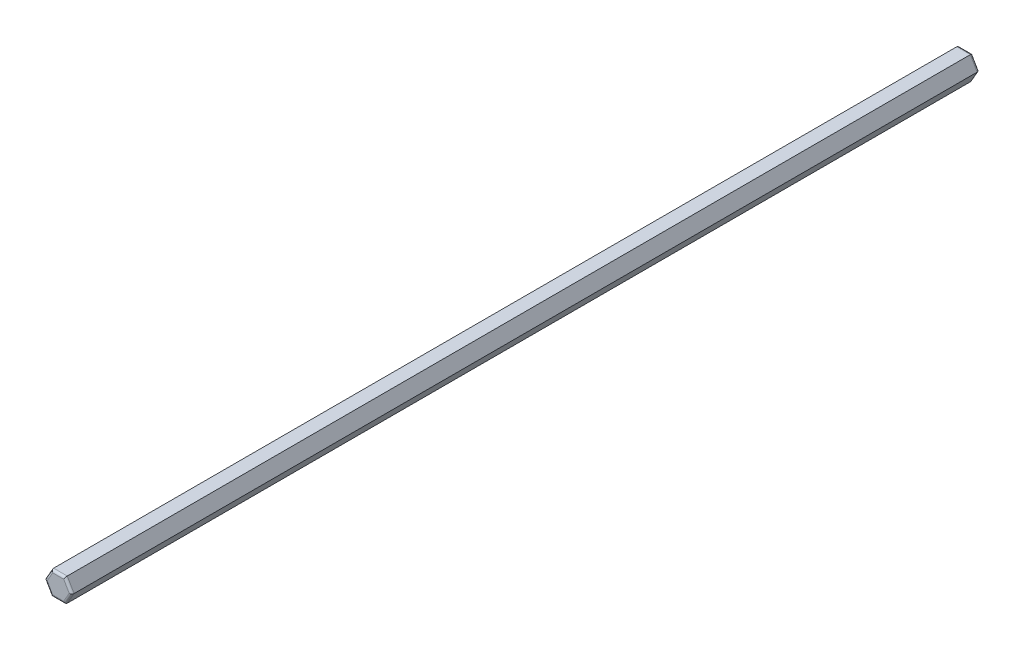
SolidWorks part; units mm, degrees
ref_plane "Front Plane" through (0, 0, 0) normal (0, 0, 1) x (1, 0, 0)
ref_plane "Top Plane" through (0, 0, 0) normal (0, 1, 0) x (1, 0, 0)
ref_plane "Right Plane" through (0, 0, 0) normal (1, 0, 0) x (0, 0, -1)
sketch "Sketch2" plane through (0, 0, 0) normal (0, 0, 1) x (1, 0, 0)
  line L1 (-0.75, 1.299) -> (-1.5, 0)
  line L2 (-1.5, 0) -> (-0.75, -1.299)
  line L3 (-0.75, -1.299) -> (0.75, -1.299)
  line L4 (0.75, -1.299) -> (1.5, 0)
  line L5 (1.5, 0) -> (0.75, 1.299)
  line L6 (0.75, 1.299) -> (-0.75, 1.299)
  circle A0 centre (0, 0) radius 1.299 construction
  dimension "D1" = 3
extrude "Boss-Extrude1" add sketch "Sketch2" along normal blind 50 and the other way blind 50
fillet "Fillet1" radius 0.25 12 edges at (1.125, -0.6495, -50) (0, -1.299, -50) (-1.125, -0.6495, -50) (-1.125, 0.6495, -50) (0, 1.299, -50) (1.125, 0.6495, -50) (-1.125, 0.6495, 50) (-1.125, -0.6495, 50) (0, -1.299, 50) (1.125, -0.6495, 50) (1.125, 0.6495, 50) (0, 1.299, 50)
